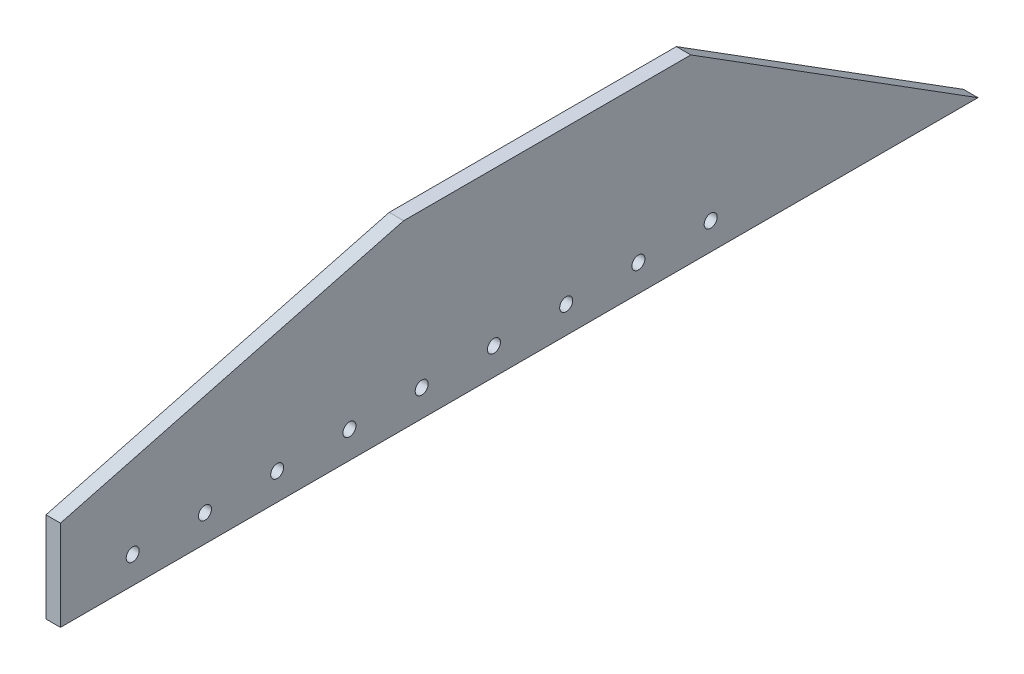
SolidWorks part; units mm, degrees
ref_plane "Front Plane" through (0, 0, 0) normal (0, 0, 1) x (1, 0, 0)
ref_plane "Top Plane" through (0, 0, 0) normal (0, 1, 0) x (1, 0, 0)
ref_plane "Right Plane" through (0, 0, 0) normal (1, 0, 0) x (0, 0, -1)
sketch "Sketch2" plane through (0, 0, 0) normal (1, 0, 0) x (0, 0, -1)
  line L0 (10.7407, 50.216) -> (90.2407, 50.216)
  line L3 (-84.2593, 0.216) -> (169.7407, 0.216)
  line L4 (-84.2593, 0.216) -> (-84.2593, 25.216)
  line L5 (-84.2593, 25.216) -> (10.7407, 50.216)
  line L6 (169.7407, 0.216) -> (90.2407, 50.216)
  circle A0 centre (-64.2593, 7.716) radius 1.8
  circle A1 centre (-44.2593, 7.716) radius 1.8
  circle A2 centre (-24.2593, 7.716) radius 1.8
  circle A3 centre (-4.2593, 7.716) radius 1.8
  circle A4 centre (15.7407, 7.716) radius 1.8
  circle A5 centre (35.7407, 7.716) radius 1.8
  circle A6 centre (55.7407, 7.716) radius 1.8
  circle A7 centre (75.7407, 7.716) radius 1.8
  circle A8 centre (95.7407, 7.716) radius 1.8
  dimension "D3" = 7.5
  dimension "D2" = 254
  dimension "D5" = 9
extrude "Boss-Extrude1" add sketch "Sketch2" along normal blind 4
